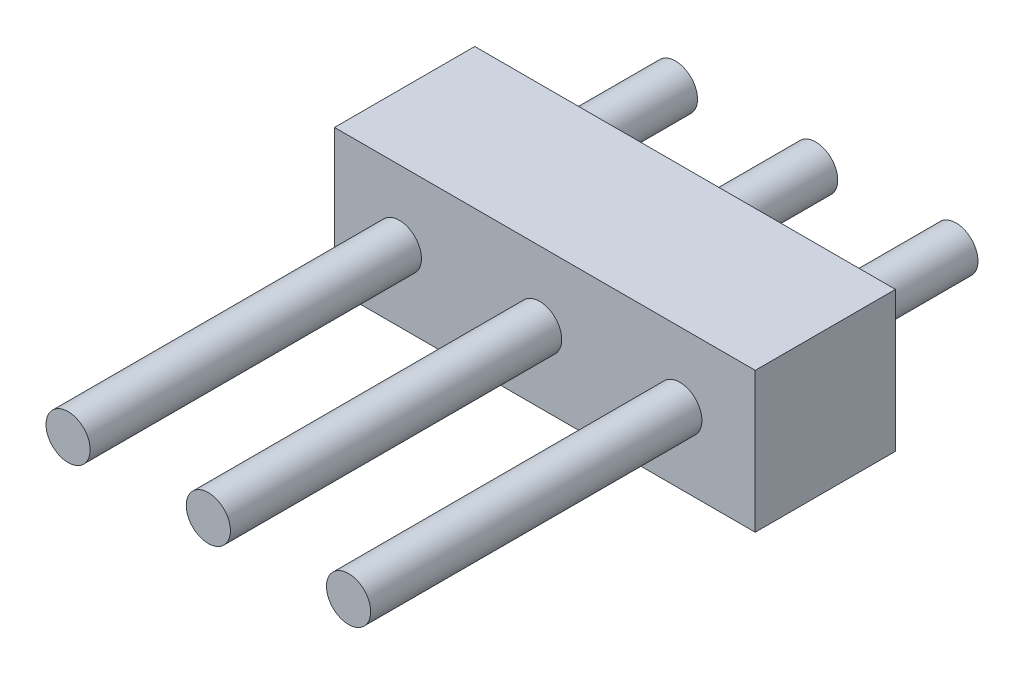
SolidWorks part; units mm, degrees
ref_plane "Спереди" through (0, 0, 0) normal (0, 0, 1) x (1, 0, 0)
ref_plane "Сверху" through (0, 0, 0) normal (0, 1, 0) x (1, 0, 0)
ref_plane "Справа" through (0, 0, 0) normal (1, 0, 0) x (0, 0, -1)
sketch "Эскиз1" plane through (0, 0, 0) normal (0, 0, 1) x (1, 0, 0)
  line L1 (0, 0) -> (7.62, 0)
  line L2 (0, 0) -> (0, 2.54)
  line L3 (0, 2.54) -> (7.62, 2.54)
  line L4 (7.62, 0) -> (7.62, 2.54)
  dimension "D1" = 7.62
  dimension "D2" = 2.54
extrude "Вытянуть1" add sketch "Эскиз1" along normal blind 2.54
sketch "Эскиз2" plane through (0, 0, 2.54) normal (0, 0, 1) x (1, 0, 0)
  line L0 (1.1744, 1.27) -> (7.0196, 1.27) construction
  line L1 (2.4444, 3.0993) -> (2.4444, -0.3033) construction
  line L2 (7.62, 2.54) -> (0, 2.54) construction
  line L3 (0, 0) -> (7.62, 0) construction
  circle A0 centre (1.1744, 1.27) radius 0.4
  circle A1 centre (3.7144, 1.27) radius 0.4
  circle A2 centre (6.2544, 1.27) radius 0.4
  dimension "D1" = 2.54
  dimension "D2" = 0.8
  dimension "D3" = 2.54
extrude "Вытянуть2" add sketch "Эскиз2" along normal blind 6 and the other way blind 5
